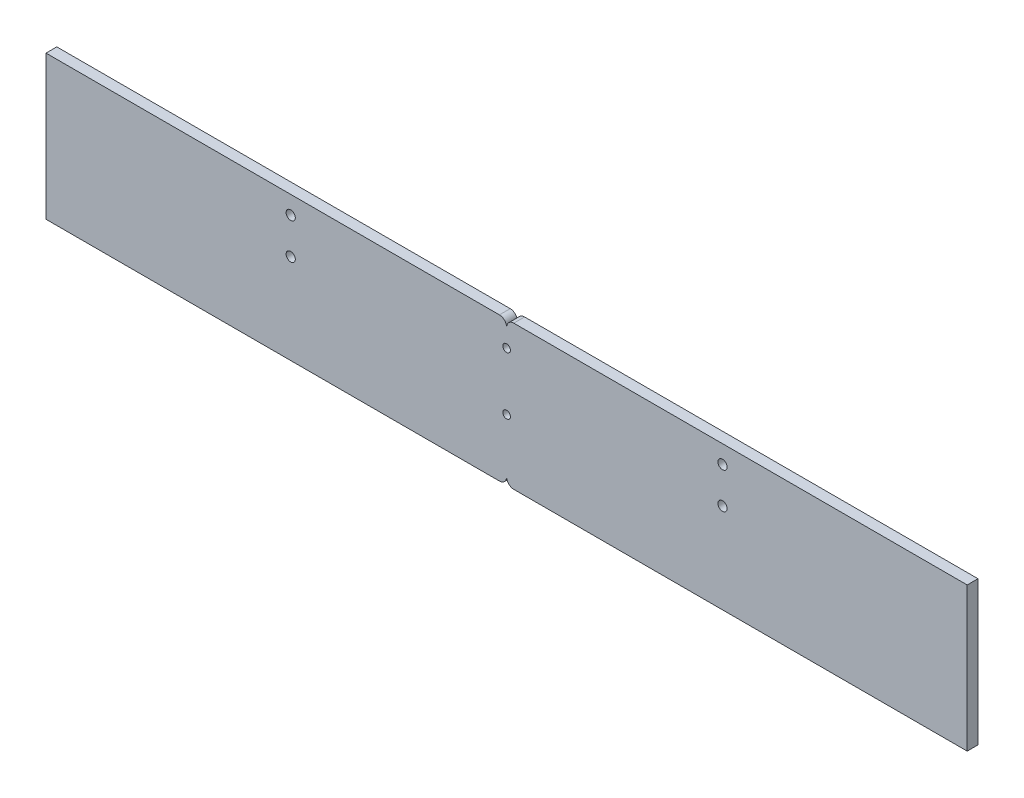
SolidWorks part; units mm, degrees
material "Клен"
ref_plane "Спереди" through (0, 0, 0) normal (0, 0, 1) x (1, 0, 0)
ref_plane "Сверху" through (0, 0, 0) normal (0, 1, 0) x (1, 0, 0)
ref_plane "Справа" through (0, 0, 0) normal (1, 0, 0) x (0, 0, -1)
sketch "Эскиз1" plane through (0, 0, 0) normal (0, 0, 1) x (1, 0, 0)
  line L0 (0, -164.4615) -> (512, -244.4615) construction
  line L1 (0, -244.4615) -> (512, -244.4615)
  line L2 (0, -244.4615) -> (0, -164.4615)
  line L3 (0, -164.4615) -> (512, -164.4615)
  line L4 (512, -244.4615) -> (512, -164.4615)
  line L5 (512, -164.4615) -> (0, -244.4615) construction
  line L6 (256, -229.8055) -> (256, -159.0937) construction
extrude "Бобышка-Вытянуть1" add sketch "Эскиз1" along normal blind 6 contours L3 L4 L1 L2
sketch "Эскиз2" plane through (0, 0, 6) normal (0, 0, 1) x (1, 0, 0)
  line L0 (0, -244.4615) -> (512, -164.4615) construction
  line L1 (512, -164.4615) -> (512, -244.4615) construction
  line L2 (512, -244.4615) -> (0, -164.4615) construction
  line L4 (256, -159.5243) -> (256, -268.7219) construction
  line L5 (259.9873, -244.4615) -> (252.0127, -244.4615)
  line L8 (0, -244.4615) -> (0, -164.4615) construction
  line L12 (0, -204.4615) -> (512, -204.4615) construction
  line L13 (0, -164.4615) -> (512, -164.4615) construction
  line L14 (0, -244.4615) -> (512, -244.4615) construction
  line L15 (259.9873, -164.4615) -> (252.0127, -164.4615)
  arc A0 (252.0127, -164.4615) -> (256, -168.4488) centre (252.0127, -168.4488) cw
  arc A1 (259.9873, -164.4615) -> (256, -168.4488) centre (259.9873, -168.4488) ccw
  arc A2 (259.9873, -244.4615) -> (256, -240.4743) centre (259.9873, -240.4743) cw
  arc A3 (252.0127, -244.4615) -> (256, -240.4743) centre (252.0127, -240.4743) ccw
  circle A4 centre (256, -178.4615) radius 2.1
  circle A9 centre (256, -210.4615) radius 2.1
  circle A10 centre (136, -174.4615) radius 2.55
  circle A11 centre (136, -194.4615) radius 2.55
  circle A12 centre (376, -174.4615) radius 2.55
  circle A13 centre (376, -194.4615) radius 2.55
  point P10 (256, -164.4615)
  point P11 (256, -244.4615)
  point P14 (0, -204.4615)
  point P16 (512, -204.4615)
  point P22 (256, -204.4615)
  point P29 (256, -164.4615)
  point P37 (256, -210.4615)
  point P39 (136, -174.4615)
  dimension "D1" = 5.1
  dimension "D2" = 5.1
  dimension "D3" = 5.1
  dimension "D4" = 5.1
extrude "Вырез-Вытянуть1" cut sketch "Эскиз2" against normal through all
equation "\"D2@Эскиз2\"=\"D1@Эскиз2\""
equation "\"D3@Эскиз2\"=\"D2@Эскиз2\""
equation "\"D4@Эскиз2\"=\"D1@Эскиз2\""
